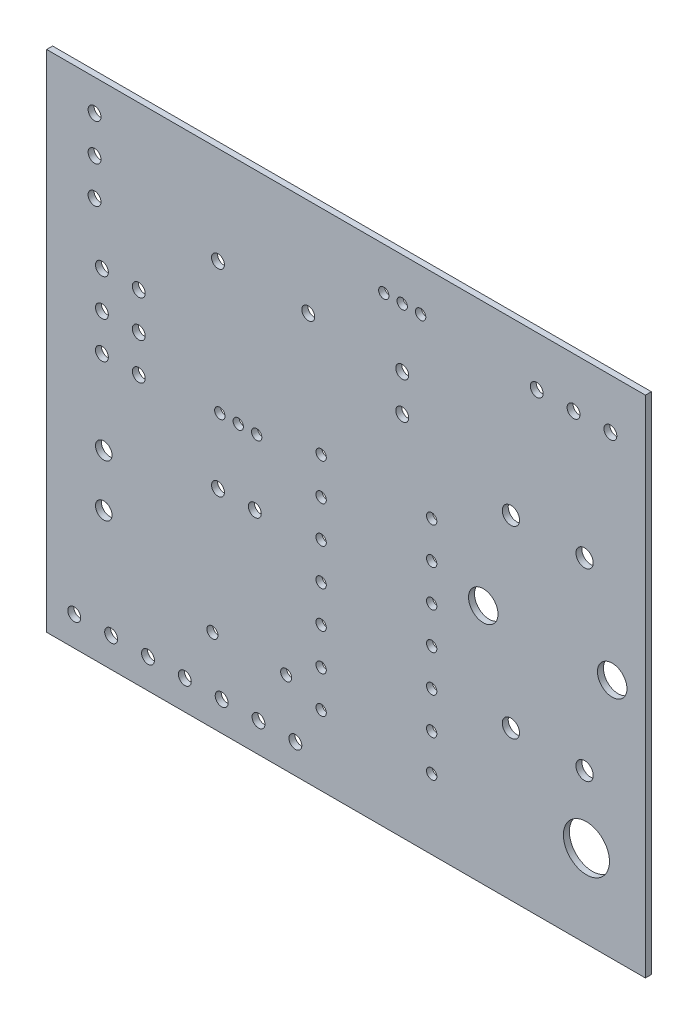
SolidWorks part; units mm, degrees
ref_plane "Alzado" through (0, 0, 0) normal (0, 0, 1) x (1, 0, 0)
ref_plane "Planta" through (0, 0, 0) normal (0, 1, 0) x (1, 0, 0)
ref_plane "Vista lateral" through (0, 0, 0) normal (1, 0, 0) x (0, 0, -1)
ref_plane "Plane1" through (0, 0, 0) normal (0, 0, -1) x (-1, 0, 0)
sketch "Sketch1" plane through (0, 0, 0) normal (0, 0, -1) x (-1, 0, 0)
  line L0 (0, 0) -> (-41.275, 0)
  line L1 (-41.275, 0) -> (-41.275, -34.798)
  line L2 (-41.275, -34.798) -> (0, -34.798)
  line L3 (0, -34.798) -> (0, 0)
  circle A0 centre (-38.862, -3.429) radius 0.4445
  circle A1 centre (-37.084, -11.811) radius 0.5969
  circle A2 centre (-33.782, -3.429) radius 0.4445
  circle A3 centre (-36.322, -3.429) radius 0.4445
  circle A4 centre (-32.004, -11.811) radius 0.5969
  circle A5 centre (-26.543, -14.732) radius 0.3556
  circle A6 centre (-26.543, -17.272) radius 0.3556
  circle A7 centre (-24.511, -2.921) radius 0.3556
  circle A8 centre (-25.781, -2.921) radius 0.3556
  circle A9 centre (-23.241, -2.921) radius 0.3556
  circle A10 centre (-24.511, -6.985) radius 0.4445
  circle A11 centre (-24.511, -9.525) radius 0.4445
  circle A12 centre (-18.923, -14.732) radius 0.3556
  circle A13 centre (-18.923, -17.272) radius 0.3556
  circle A14 centre (-30.099, -18.161) radius 1.016
  circle A15 centre (-38.989, -18.161) radius 1.016
  circle A16 centre (-26.543, -19.812) radius 0.3556
  circle A17 centre (-26.543, -22.352) radius 0.3556
  circle A18 centre (-37.084, -24.511) radius 0.5969
  circle A19 centre (-37.211, -29.083) radius 1.5875
  circle A20 centre (-32.004, -24.511) radius 0.5969
  circle A21 centre (-26.543, -24.892) radius 0.3556
  circle A22 centre (-26.543, -27.432) radius 0.3556
  circle A23 centre (-18.923, -19.812) radius 0.3556
  circle A24 centre (-18.923, -22.352) radius 0.3556
  circle A25 centre (-18.923, -27.432) radius 0.3556
  circle A26 centre (-26.543, -29.972) radius 0.3556
  circle A27 centre (-18.923, -29.972) radius 0.3556
  circle A28 centre (-11.811, -6.731) radius 0.4445
  circle A29 centre (-18.034, -6.731) radius 0.4445
  circle A30 centre (-6.35, -11.176) radius 0.4445
  circle A31 centre (-6.35, -13.716) radius 0.4445
  circle A32 centre (-13.208, -15.748) radius 0.3556
  circle A33 centre (-14.478, -15.748) radius 0.3556
  circle A34 centre (-11.938, -15.748) radius 0.3556
  circle A35 centre (-3.302, -7.239) radius 0.4445
  circle A36 centre (-3.81, -11.176) radius 0.4445
  circle A37 centre (-3.302, -2.159) radius 0.4445
  circle A38 centre (-3.302, -4.699) radius 0.4445
  circle A39 centre (-3.81, -13.716) radius 0.4445
  circle A40 centre (-6.35, -16.256) radius 0.4445
  circle A41 centre (-3.81, -16.256) radius 0.4445
  circle A42 centre (-18.923, -24.892) radius 0.3556
  circle A43 centre (-16.51, -29.083) radius 0.381
  circle A44 centre (-11.811, -20.32) radius 0.4445
  circle A45 centre (-14.351, -20.32) radius 0.4445
  circle A46 centre (-14.605, -32.766) radius 0.4445
  circle A47 centre (-17.145, -32.766) radius 0.4445
  circle A48 centre (-12.065, -32.766) radius 0.4445
  circle A49 centre (-11.43, -29.083) radius 0.381
  circle A50 centre (-9.525, -32.766) radius 0.4445
  circle A51 centre (-3.937, -21.971) radius 0.5715
  circle A52 centre (-3.937, -25.5524) radius 0.5715
  circle A53 centre (-4.445, -32.766) radius 0.4445
  circle A54 centre (-6.985, -32.766) radius 0.4445
  circle A55 centre (-1.905, -32.766) radius 0.4445
extrude "Boss-Extrude1" add sketch "Sketch1" against normal blind 0.4115
sketch "Sketch2" plane through (0, 0, 0.4115) normal (0, 0, 1) x (1, 0, 0)
  line L0 (-19.5465, -40.0131) -> (72.0906, -40.0131) construction
sketch "Sketch3" plane through (0, 0, 0) normal (0, 0, -1) x (-1, 0, 0)
  line L0 (-32.2914, -44.1871) -> (-1.4201, -44.1871) construction
